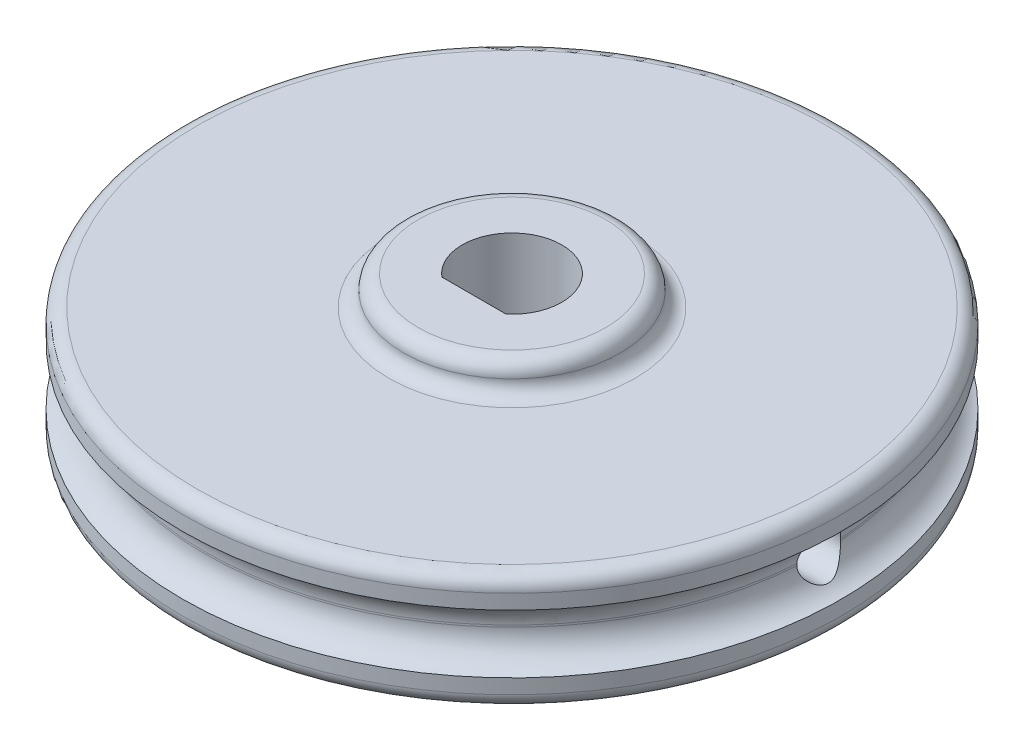
SolidWorks part; units mm, degrees
ref_plane "Front Plane" through (0, 0, 0) normal (0, 0, 1) x (1, 0, 0)
ref_plane "Top Plane" through (0, 0, 0) normal (0, 1, 0) x (1, 0, 0)
ref_plane "Right Plane" through (0, 0, 0) normal (1, 0, 0) x (0, 0, -1)
sketch "Sketch1" plane through (0, 0, 0) normal (0, 1, 0) x (1, 0, 0)
  line L0 (-1.0954, -1.3) -> (1.0954, -1.3)
  line L1 (0, -1.3) -> (0, -1.7)
  circle A0 centre (0, 0) radius 1.7
  circle A1 centre (0, 0) radius 11.25
  dimension "D1" = 3.4
  dimension "D2" = 22.5
  dimension "D3" = 0.4
extrude "Boss-Extrude1" add sketch "Sketch1" along normal blind 4 contours A1 A0 | L1 A0 L0 | L0 A0 L1 region at (-0.4181, 0, 1.4617) region at (0.4181, 0, 1.4617) region at (-10.9318, 0, 0)
sketch "Sketch2" plane through (0, 4, 0) normal (0, 1, 0) x (1, 0, 0)
  line L1 (1.7, 0) -> (3.7, 0) construction
  line L2 (-1.0954, -1.3) -> (1.0954, -1.3)
  circle A0 centre (0, 0) radius 3.7
  arc A1 (1.0954, -1.3) -> (-1.0954, -1.3) centre (0, 0) ccw construction
  arc A2 (-1.0954, -1.3) -> (1.0954, -1.3) centre (0, 0) cw
  dimension "D2" = 1.7
  dimension "D1" = 2
extrude "Boss-Extrude2" add sketch "Sketch2" along normal blind 1
sketch "Sketch3" plane through (0, 5, 0) normal (0, 1, 0) x (1, 0, 0)
  line L0 (0, 0) -> (0, -3.7) construction
  circle A0 centre (0, 0) radius 3.7 construction
sketch "Sketch4" plane through (0, 0, 0) normal (0, -1, 0) x (1, 0, 0)
  line L0 (0, 0) -> (0, 11.25) construction
  circle A0 centre (0, 0) radius 11.25 construction
ref_plane "Plane1" through (0, 0, 0) normal (1, 0, 0) x (0, 0, -1)
ref_plane "Plane2" through (12.5, 0, 0) normal (1, 0, 0) x (0, 0, -1)
sketch "Sketch5" plane through (12.5, 0, 0) normal (1, 0, 0) x (0, 0, -1)
  line L0 (0, 0) -> (0, 4) construction
  line L4 (11.25, 4) -> (-11.25, 4) construction
  circle A0 centre (0, 2) radius 0.75
  dimension "D1" = 1.5
sketch3d "3DSketch1"
  line L0 (12.5, 0, 0) -> (12.5, 4, 0) construction
  line L1 (12.5, 2, 0) -> (9.1368, 2, 0)
  line L3 (9.1368, 2, 0) -> (7.1368, 2, 0) construction
  line L4 (7.1368, 0, 0) -> (7.1368, -2.2816, 0)
  arc A0 (7.1368, 0, 0) -> (9.1368, 2, 0) centre (9.1368, 0, 0) ccw
  point P6 (7.1368, 2, 0)
  point P8 (9.1368, 0, -2)
  dimension "D1" = 2
sweep "Cut-Sweep1" cut path "3DSketch1" circular profile diameter 1.5 parameters "D3"=1.5
mirror "Mirror1" about plane through (0, 0, 0) normal (1, 0, 0) of "Cut-Sweep1"
ref_plane "Plane3" through (0, 2, 0) normal (0, 1, 0) x (1, 0, 0)
sketch "Sketch21" plane through (0, 2, 0) normal (0, 1, 0) x (1, 0, 0)
  circle A0 centre (0, 0) radius 12.5
  circle A1 centre (0, 0) radius 10.5
  dimension "D1" = 25
  dimension "D2" = 2
extrude "Cut-Extrude1" cut sketch "Sketch21" against normal mid plane 2
fillet "Fillet1" radius 1 2 edges at (0, 1, 10.5) (0, 3, 10.5)
fillet "Fillet2" radius 0.5 4 edges at (0, 4, 3.7) (0, 5, 3.7) (0, 0, 11.25) (0, 4, 11.25)
